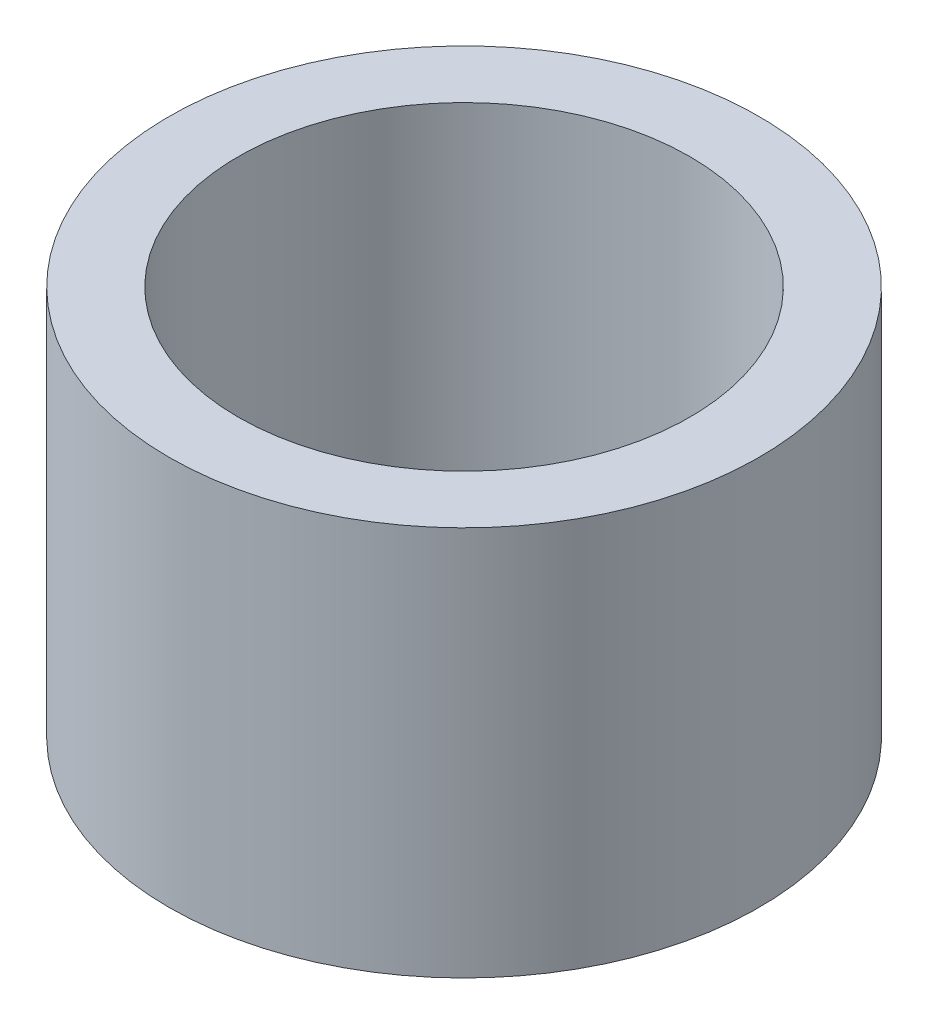
SolidWorks part; units mm, degrees
ref_plane "Front Plane" through (0, 0, 0) normal (0, 0, 1) x (1, 0, 0)
ref_plane "Top Plane" through (0, 0, 0) normal (0, 1, 0) x (1, 0, 0)
ref_plane "Right Plane" through (0, 0, 0) normal (1, 0, 0) x (0, 0, -1)
sketch "Sketch1" plane through (0, 0, 0) normal (0, 1, 0) x (1, 0, 0)
  circle A0 centre (0, 0) radius 30
  dimension "SLEEVE_OD" = 60
extrude "Boss-Extrude1" add sketch "Sketch1" along normal blind 39.6313
sketch "Sketch2" plane through (0, 0, 0) normal (0, 1, 0) x (1, 0, 0)
  circle A0 centre (0, 0) radius 22.9509
  dimension "BORE_D" = 45.9018
extrude "Cut-Extrude1" cut sketch "Sketch2" along normal through all
chamfer "Chamfer1" distance 3.1384 angle 60.99 rebuild error yes
